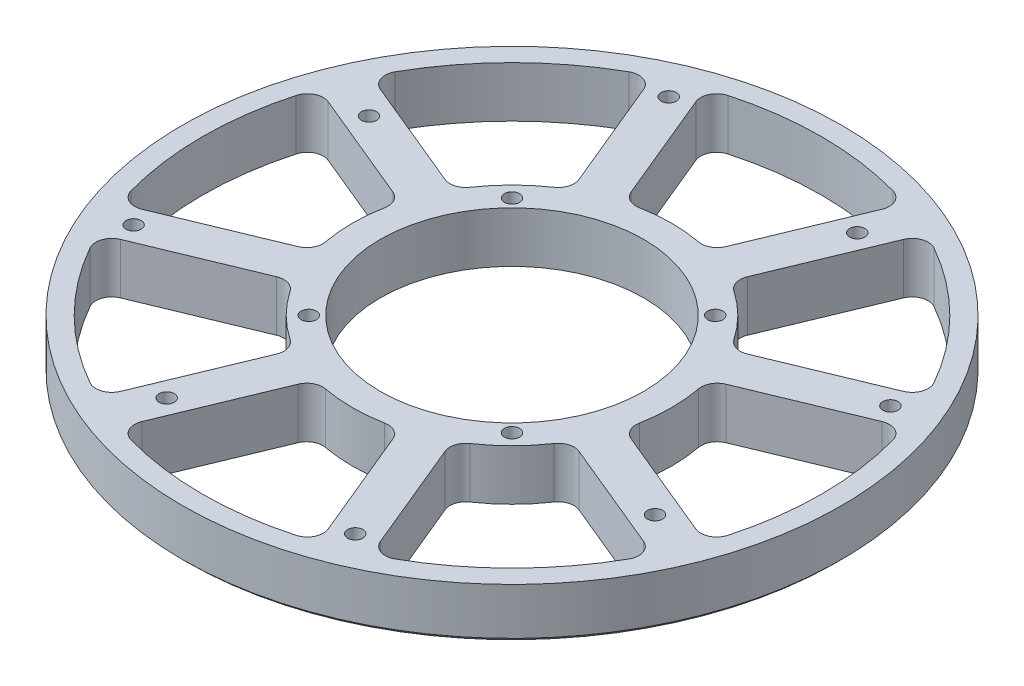
SolidWorks part; units mm, degrees
material "6061-T6 (SS)"
ref_plane "Front Plane" through (0, 0, 0) normal (0, 0, 1) x (1, 0, 0)
ref_plane "Top Plane" through (0, 0, 0) normal (0, 1, 0) x (1, 0, 0)
ref_plane "Right Plane" through (0, 0, 0) normal (1, 0, 0) x (0, 0, -1)
sketch "Sketch2" plane through (0, 0, 0) normal (1, 0, 0) x (0, 0, -1)
  line L0 (0, 0) -> (-82.55, 0)
  line L1 (-82.55, 0) -> (-82.55, 12.7)
  line L2 (-82.55, 12.7) -> (0, 12.7)
  line L5 (0, 12.7) -> (0, 0)
  dimension "D1" = 82.55
  dimension "D2" = 12.7
ref_axis "Axis1" through (0, -0.635, 0) along (0, 1, 0)
revolve "Revolve1" add sketch "Sketch2" angle 360 about axis through (0, -0.635, 0) along (0, 1, 0)
hole_wizard "#10-24 Tapped Hole1" positions "Sketch6" profile "Sketch7" tap size "#10-24" standard "ANSI Inch" end condition through all
sketch "Sketch6" plane through (0, 12.7, 0) normal (0, 1, 0) x (1, 0, 0)
  line L0 (0, 0) -> (-53.438, 129.0108) construction
  line L2 (0, 0) -> (0, 109.0908) construction
  line L3 (0, 0) -> (-76.2663, 31.5905) construction
  line L4 (0, 0) -> (-68.4315, 68.4315) construction
  circle A0 centre (0, 0) radius 82.55 construction
  point P0 (-27.7637, 67.0275)
  point P18 (-61.1608, 25.3336)
  point P27 (-25.4558, 25.4558)
  dimension "D1" = 22.5
  dimension "D2" = 72.55
  dimension "D3" = 45
  dimension "D4" = 66.2
  dimension "D6" = 22.5
  dimension "D5" = 36
sketch "Sketch7" plane through (-27.7637, 12.7, -67.0275) normal (1, 0, 0) x (0, 0, 1)
  line L0 (0, 0) -> (0, 12.7)
  line L1 (0, 12.7) -> (1.8986, 12.7)
  line L2 (1.8986, 12.7) -> (1.8986, 0)
  line L5 (1.8986, 0) -> (0, 0)
  line L11 (0, -6.35) -> (0, 107.95) construction
  dimension "Thread Major Dia." = 3.7973
  dimension "Thru Tap Drill Depth" = 12.7
pattern_circular "CirPattern3" count 4 over 360 about axis through (0, -0.635, 0) along (0, 1, 0) of "#10-24 Tapped Hole1"
sketch "Sketch8" plane through (0, 12.7, 0) normal (0, 1, 0) x (1, 0, 0)
  line L4 (0, 0) -> (0, 93.9995) construction
  line L5 (0, 0) -> (113.8372, 0) construction
  line L6 (-10.5679, 38.5787) -> (-24.996, 73.4112)
  line L7 (10.5679, 38.5787) -> (24.996, 73.4112)
  line L8 (0, 0) -> (-27.7637, 67.0275) construction
  arc A0 (-10.5679, 38.5787) -> (10.5679, 38.5787) centre (0, 0) cw
  arc A1 (-24.996, 73.4112) -> (24.996, 73.4112) centre (0, 0) cw
  circle A2 centre (0, 0) radius 82.55 construction
  dimension "D1" = 40
  dimension "D2" = 5
  dimension "D3" = 5
extrude "Cut-Extrude1" cut sketch "Sketch8" against normal through all
fillet "Fillet1" radius 4 4 edges at (10.5679, 6.35, -38.5787) (24.996, 6.35, -73.4112) (-10.5679, 6.35, -38.5787) (-24.996, 6.35, -73.4112)
pattern_circular "CirPattern4" count 8 over 360 about axis through (0, -0.635, 0) along (0, 1, 0) of "Cut-Extrude1", "Fillet1"
chamfer "Chamfer2" distance 1 angle 45 1 edges at (0, 0, -82.55)
sketch "Sketch9" plane through (0, 12.7, 0) normal (0, 1, 0) x (1, 0, 0)
  circle A0 centre (0, 0) radius 33
  dimension "D1" = 66
extrude "Cut-Extrude2" cut sketch "Sketch9" against normal through all
equation "\"TubeDiameter\" = 6.500in"
equation "\"D1@Sketch2\"=\"TubeDiameter\"/2"
equation "\"D2@Sketch6\"=\"TubeDiameter\"/2-10mm"
